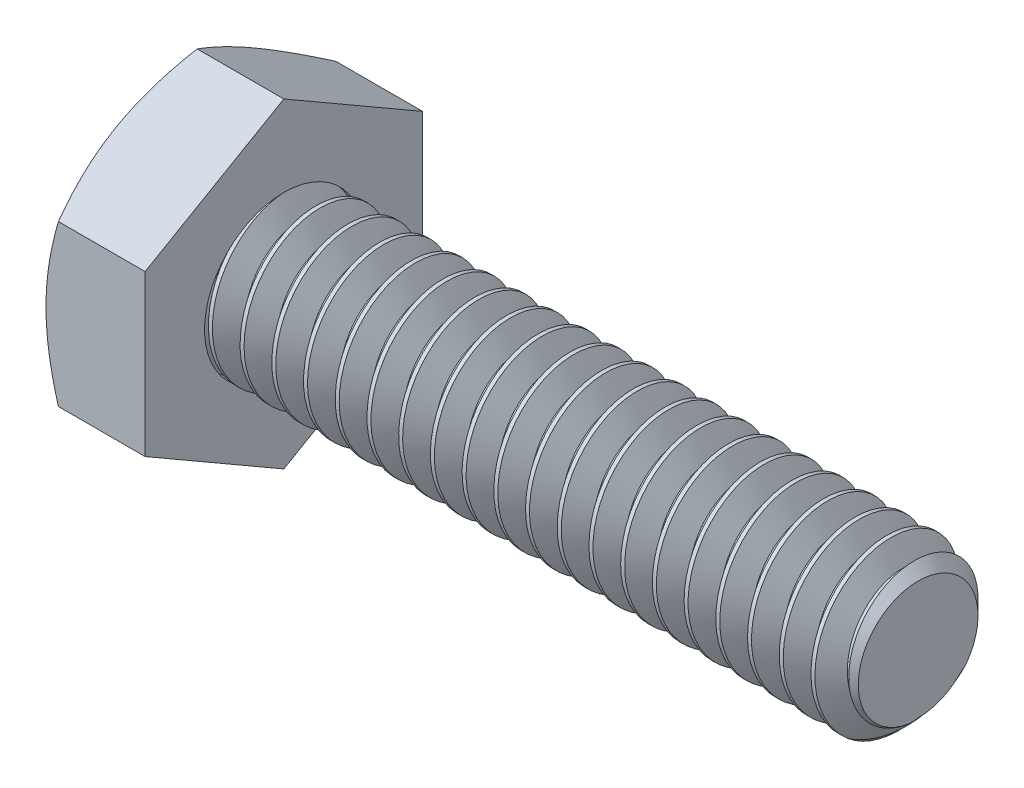
SolidWorks part; units mm, degrees
ref_plane "Front Plane" through (0, 0, 0) normal (0, 0, 1) x (1, 0, 0)
ref_plane "Top Plane" through (0, 0, 0) normal (0, 1, 0) x (1, 0, 0)
ref_plane "Right Plane" through (0, 0, 0) normal (1, 0, 0) x (0, 0, -1)
sketch "Sketch1" plane through (0, 0, 0) normal (0, 0, 1) x (1, 0, 0)
  line L0 (-14.6844, 0) -> (14.6844, 0) construction
  line L1 (14.6844, 3.175) -> (14.6844, -3.175) construction
  line L2 (-10.7156, 5.5562) -> (-10.7156, -5.5562) construction
  line L3 (-14.6844, 5.5562) -> (-14.6844, -5.5562) construction
  line L4 (14.605, 3.3125) -> (15.875, 3.3125) construction
  line L5 (15.875, 3.3125) -> (15.24, 2.2126) construction
  line L6 (15.24, 2.2126) -> (14.605, 3.3125) construction
  line L7 (14.6447, 3.2437) -> (15.8353, 3.2437) construction
  line L8 (15.24, 3.3125) -> (15.24, 3.175) construction
  line L9 (14.6844, 3.175) -> (15.7956, 3.175) construction
  line L10 (15.3194, 2.3501) -> (15.1606, 2.3501) construction
  line L11 (15.24, 2.3501) -> (15.24, 2.2126) construction
  point P9 (-10.7156, 0)
  point P10 (10.2394, -3.175)
  point P23 (15.24, 3.2437)
  dimension "D2" = 0.1588
  dimension "D1" = 4.445
  dimension "Screw Size Decimal Equivalent" = 6.35
  dimension "Head Width" = 11.1125
  dimension "Head Height" = 3.9688
  dimension "Length" = 25.4
  dimension "Thread Pitch" = 1.27
ref_plane "Plane2" through (14.6844, 0, 0) normal (1, 0, 0) x (0, 0, -1)
sketch "Sketch5" plane through (14.6844, 0, 0) normal (1, 0, 0) x (0, 0, -1)
  circle A0 centre (0, 0) radius 3.175
extrude "Boss-Extrude3" add sketch "Sketch5" against normal up to vertex (25.4 mm away) up to point (-10.7156, 0, 0)
sketch "Sketch9" plane through (14.6844, 0, 0) normal (1, 0, 0) x (0, 0, -1)
  circle A1 centre (0, 0) radius 3.175
  circle A2 centre (0, 0) radius 3.175
  dimension "D1" = 0
sketch "Sketch6" plane through (-10.7156, 0, 0) normal (-1, 0, 0) x (0, 0, 1)
  line L0 (0, 5.5562) -> (0, -5.5562) construction
  line L1 (5.5563, 3.2079) -> (0, 6.4158)
  line L2 (0, 6.4158) -> (-5.5562, 3.2079)
  line L3 (-5.5562, 3.2079) -> (-5.5562, -3.2079)
  line L4 (-5.5562, -3.2079) -> (0, -6.4158)
  line L5 (0, -6.4158) -> (5.5563, -3.2079)
  line L6 (5.5563, -3.2079) -> (5.5563, 3.2079)
  circle A0 centre (0, 0) radius 5.5563 construction
extrude "Boss-Extrude4" add sketch "Sketch6" along normal up to vertex (3.9688 mm away) up to point (-14.6844, -5.5562, 0)
sketch "Sketch7" plane through (-14.6844, 0, 0) normal (-1, 0, 0) x (0, 0, 1)
  circle A0 centre (0, 0) radius 5.5563 construction
  circle A1 centre (0, 0) radius 5.5563
sketch "Sketch8" plane through (-14.6844, 0, 0) normal (-1, 0, 0) x (0, 0, 1)
  circle A0 centre (0, 0) radius 5.5563 construction
  circle A1 centre (0, 0) radius 5.5563
extrude "Cut-Extrude3" cut sketch "Sketch8" against normal through all draft 60 flip side to cut
sketch "Sketch12" plane through (-14.6844, 0, 0) normal (-1, 0, 0) x (0, 0, 1)
  line L0 (0, 4.2783) -> (0, 2.3892) construction
  line L1 (0.1667, 4.2783) -> (0.1667, 2.3892)
  line L2 (-0.1667, 4.2783) -> (-0.1667, 2.3892)
  line L3 (0, 3.175) -> (0, -3.175) construction
  arc A0 (0.1667, 4.2783) -> (-0.1667, 4.2783) centre (0, 4.2783) ccw
  arc A1 (-0.1667, 2.3892) -> (0.1667, 2.3892) centre (0, 2.3892) ccw
  circle A3 centre (0, 0) radius 2.2225 construction
  circle A4 centre (0, 0) radius 4.445 construction
  point P2 (0, 3.3337)
  dimension "D1" = 4.445
  dimension "D3" = 8.89
  dimension "D2" = 0.3334
extrude "Cut-Extrude4" cut sketch "Sketch12" against normal blind 0.254
pattern_circular "CirPattern1" count 3 over 360 about axis through (0, 0, 0) along (1, 0, 0) of "Cut-Extrude4"
curve "Helix/Spiral1" pitch 1.27 height 26.67 turns 21 parameters "Pitch"=1.27
chamfer "Chamfer1" distance 0.7772 angle 45 1 edges at (14.6844, 0, -3.175)
sketch "Sketch10" plane through (0, 0, 0) normal (0, 0, 1) x (1, 0, 0)
  line L0 (14.6844, 3.175) -> (15.1606, 2.3501)
  line L1 (15.1606, 2.3501) -> (15.3194, 2.3501)
  line L2 (15.3194, 2.3501) -> (15.7956, 3.175)
  line L3 (14.6844, 3.175) -> (15.7956, 3.175)
  line L4 (15.24, 3.175) -> (15.24, 2.3501) construction
  line L5 (14.9225, 2.7626) -> (15.5575, 2.7626) construction
  dimension "D1" = 60
  dimension "D2" = 0.1588
  dimension "D3" = 0.635
sweep "Cut-Sweep1" cut profiles "Sketch10" path "Helix/Spiral1"
equation "\"D2@Sketch10\" = \"Pitch@Helix/Spiral1\"*.125"
equation "\"D3@Sketch10\" = \"Pitch@Helix/Spiral1\"*.5"
equation "\"D1@Chamfer1\"= \"Pitch@Helix/Spiral1\" * .612"
equation "\"D1@Sketch12\" = \"Head Width@Sketch1\" * .4"
equation "\"D3@Sketch12\" = \"Head Width@Sketch1\" * .8"
equation "\"D2@Sketch12\" = \"Head Width@Sketch1\" * .03"
equation "\"D1@Sketch1\" = \"Pitch@Helix/Spiral1\"*3.5"
equation "\"D3@Helix/Spiral1\"=\"Length@Sketch1\" + \"Thread Pitch@Sketch1\""
equation "\"D2@Sketch1\"=\"Thread Pitch@Sketch1\"/8"
equation "\"Pitch@Helix/Spiral1\"=\"Thread Pitch@Sketch1\""
